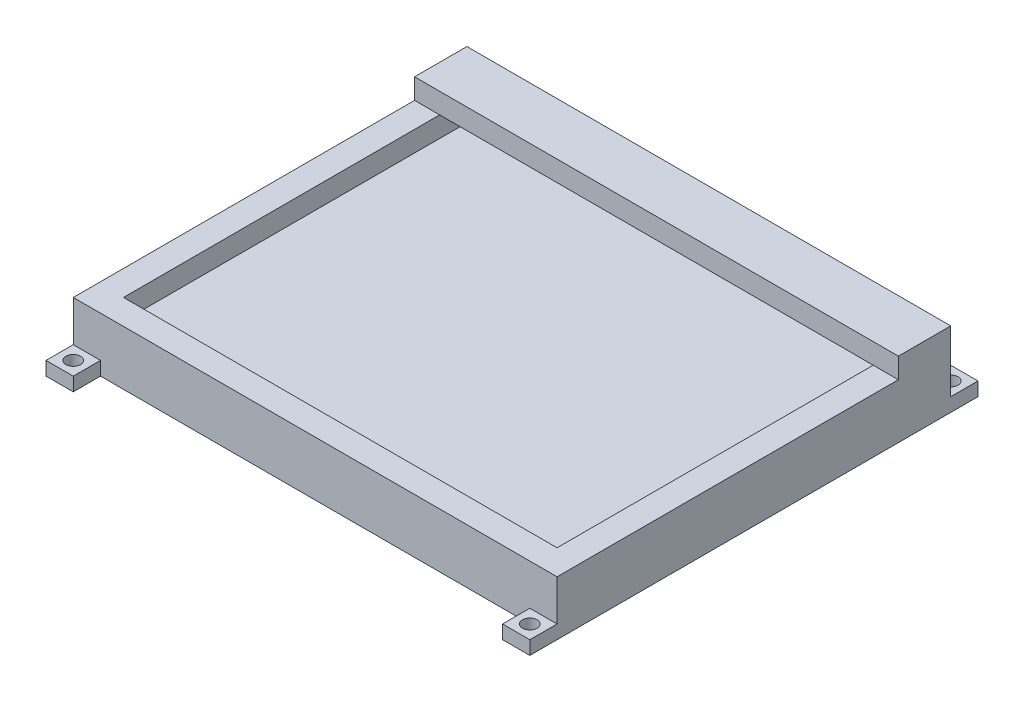
SolidWorks part; units mm, degrees
ref_plane "Front Plane" through (0, 0, 0) normal (0, 0, 1) x (1, 0, 0)
ref_plane "Top Plane" through (0, 0, 0) normal (0, 1, 0) x (1, 0, 0)
ref_plane "Right Plane" through (0, 0, 0) normal (1, 0, 0) x (0, 0, -1)
sketch "Sketch1" plane through (0, 0, 0) normal (0, 1, 0) x (1, 0, 0)
  line L1 (0, 0) -> (112.7, 0)
  line L2 (0, 0) -> (0, 91.7)
  line L3 (0, 91.7) -> (112.7, 91.7)
  line L4 (112.7, 0) -> (112.7, 91.7)
  dimension "D1" = 112.7
  dimension "D2" = 91.7
extrude "Boss-Extrude1" add sketch "Sketch1" along normal blind 12.7
sketch "Sketch2" plane through (0, 12.7, 0) normal (0, 1, 0) x (1, 0, 0)
  line L0 (0, 0) -> (112.7, 0) construction
  line L1 (5.85, 5.85) -> (106.85, 5.85)
  line L2 (5.85, 5.85) -> (5.85, 85.85)
  line L3 (5.85, 85.85) -> (106.85, 85.85)
  line L4 (106.85, 5.85) -> (106.85, 85.85)
  line L5 (0, 91.7) -> (0, 0) construction
  dimension "D1" = 101
  dimension "D2" = 80
  dimension "D3" = 5.85
  dimension "D4" = 5.85
extrude "Cut-Extrude1" cut sketch "Sketch2" against normal blind 4.7625
sketch "Sketch3" plane through (0, 0, 0) normal (0, -1, 0) x (1, 0, 0)
  line L1 (112.7, 0) -> (106.35, 0)
  line L2 (112.7, 0) -> (112.7, 6.35)
  line L3 (112.7, 6.35) -> (106.35, 6.35)
  line L4 (106.35, 0) -> (106.35, 6.35)
  line L5 (0, 0) -> (6.35, 0)
  line L6 (0, 0) -> (0, 6.35)
  line L7 (0, 6.35) -> (6.35, 6.35)
  line L8 (6.35, 0) -> (6.35, 6.35)
  line L9 (0, -91.7) -> (6.35, -91.7)
  line L10 (0, -91.7) -> (0, -98.05)
  line L11 (0, -98.05) -> (6.35, -98.05)
  line L12 (6.35, -91.7) -> (6.35, -98.05)
  line L13 (112.7, -91.7) -> (106.35, -91.7)
  line L14 (112.7, -91.7) -> (112.7, -98.05)
  line L15 (112.7, -98.05) -> (106.35, -98.05)
  line L16 (106.35, -91.7) -> (106.35, -98.05)
  circle A0 centre (3.175, 3.175) radius 1.7
  circle A1 centre (109.525, 3.175) radius 1.7
  circle A2 centre (3.175, -94.875) radius 1.7
  circle A3 centre (109.525, -94.875) radius 1.7
  dimension "D9" = 3.4
  dimension "D10" = 3.4
  dimension "D11" = 3.4
  dimension "D12" = 3.4
  dimension "D1" = 6.35
  dimension "D2" = 6.35
  dimension "D3" = 6.35
  dimension "D4" = 6.35
  dimension "D5" = 6.35
  dimension "D6" = 6.35
  dimension "D7" = 6.35
  dimension "D8" = 6.35
extrude "Boss-Extrude2" add sketch "Sketch3" against normal blind 3.175
sketch "Sketch4" plane through (0, 12.7, 0) normal (0, 1, 0) x (1, 0, 0)
  line L0 (112.7, 0) -> (112.7, 91.7) construction
  line L1 (0, 91.7) -> (112.7, 91.7)
  line L2 (0, 91.7) -> (0, 79.5)
  line L3 (0, 79.5) -> (112.7, 79.5)
  line L4 (112.7, 91.7) -> (112.7, 79.5)
  line L5 (106.85, 85.85) -> (5.85, 85.85) construction
  dimension "D1" = 12.2
  dimension "D2" = 5.85
extrude "Boss-Extrude3" add sketch "Sketch4" along normal blind 4.7625
